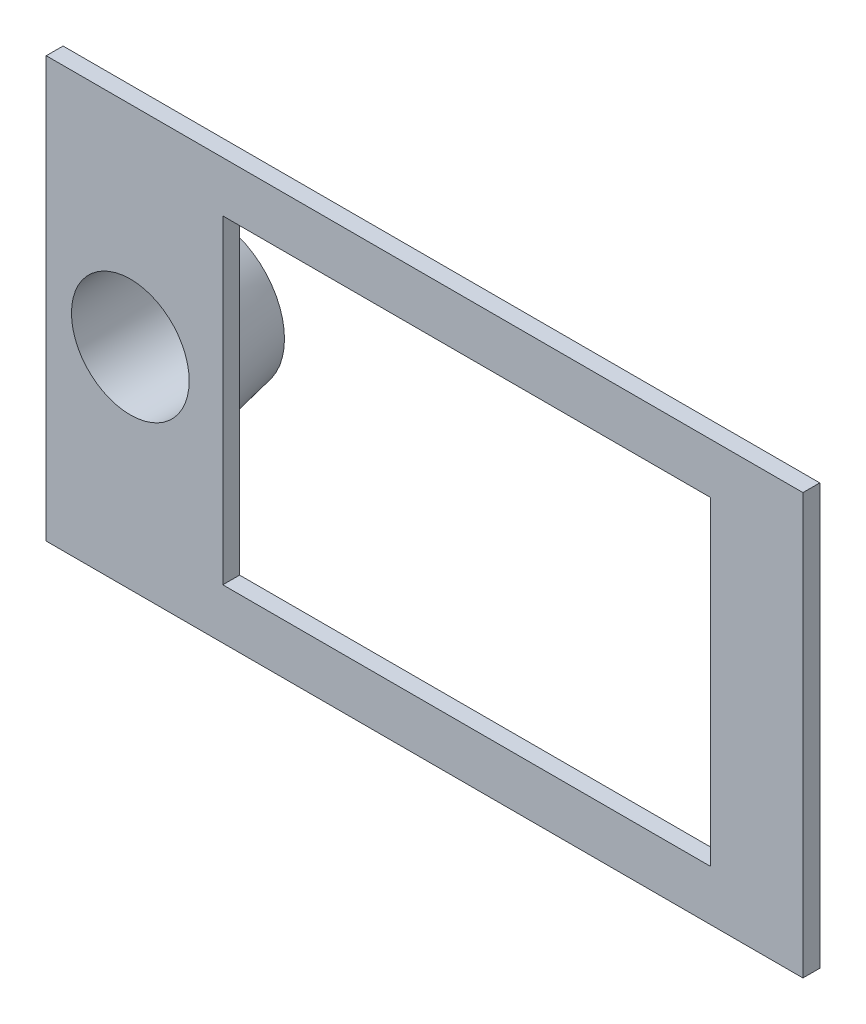
SolidWorks part; units mm, degrees
material "ABS"
ref_plane "前视基准面" through (0, 0, 0) normal (0, 0, 1) x (1, 0, 0)
ref_plane "上视基准面" through (0, 0, 0) normal (0, 1, 0) x (1, 0, 0)
ref_plane "右视基准面" through (0, 0, 0) normal (1, 0, 0) x (0, 0, -1)
sketch "草图1" plane through (0, 0, 902.9445) normal (0, 0, -1) x (-1, 0, 0)
  line L1 (-153, 72) -> (-18, 72)
  line L2 (-153, 72) -> (-153, -3)
  line L3 (-153, -3) -> (-18, -3)
  line L4 (-18, 72) -> (-18, -3)
  line L5 (-136.5, 63) -> (-49.5, 63)
  line L6 (-136.5, 63) -> (-136.5, 6)
  line L7 (-136.5, 6) -> (-49.5, 6)
  line L8 (-49.5, 63) -> (-49.5, 6)
  line L10 (-21, 0) -> (-21, 69) construction
  line L11 (-18, 72) -> (-153, 72) construction
  circle A0 centre (-33, 34.5) radius 10.5
  dimension "D1" = 21
  dimension "D2" = 3
  dimension "D3" = 12
  dimension "D4" = 28.5
  dimension "D5" = 115.5
  dimension "D6" = 132
  dimension "D7" = 9
  dimension "D8" = 37.5
  dimension "D9" = 66
  dimension "D10" = 75
extrude "凸台-拉伸1" add sketch "草图1" along normal blind 3
ref_plane "基准面4" through (0, 0, 887.9445) normal (0, 0, 1) x (1, 0, 0)
sketch "草图4" plane through (0, 0, 887.9445) normal (0, 0, 1) x (1, 0, 0)
  circle A0 centre (33, 34.5) radius 10.5
  circle A1 centre (33, 34.5) radius 12.5
  point P5 (0, 0)
  dimension "D1" = 21
  dimension "D2" = 25
  dimension "D3" = 33
  dimension "D4" = 34.5
sketch "草图5" plane through (0, 0, 899.9445) normal (0, 0, -1) x (-1, 0, 0)
  line L1 (-153, 72) -> (-153, -3) construction
  line L2 (-49.5, 63) -> (-136.5, 63) construction
  circle A0 centre (-33, 34.5) radius 10.5
  circle A1 centre (-33, 34.5) radius 15
  dimension "D1" = 21
  dimension "D2" = 30
  dimension "D3" = 120
  dimension "D4" = 28.5
loft "放样4" add section "草图5" section "草图4" connector at (33.6326, 19.5133, 899.9445) connector at (33.5463, 22.0119, 887.9445)
extrude "切除-拉伸1" cut sketch "草图5<93>" along normal up to next contours A0
sketch "草图5<93>" plane through (0, 0, 899.9445) normal (0, 0, -1) x (-1, 0, 0) same geometry as "草图5"
